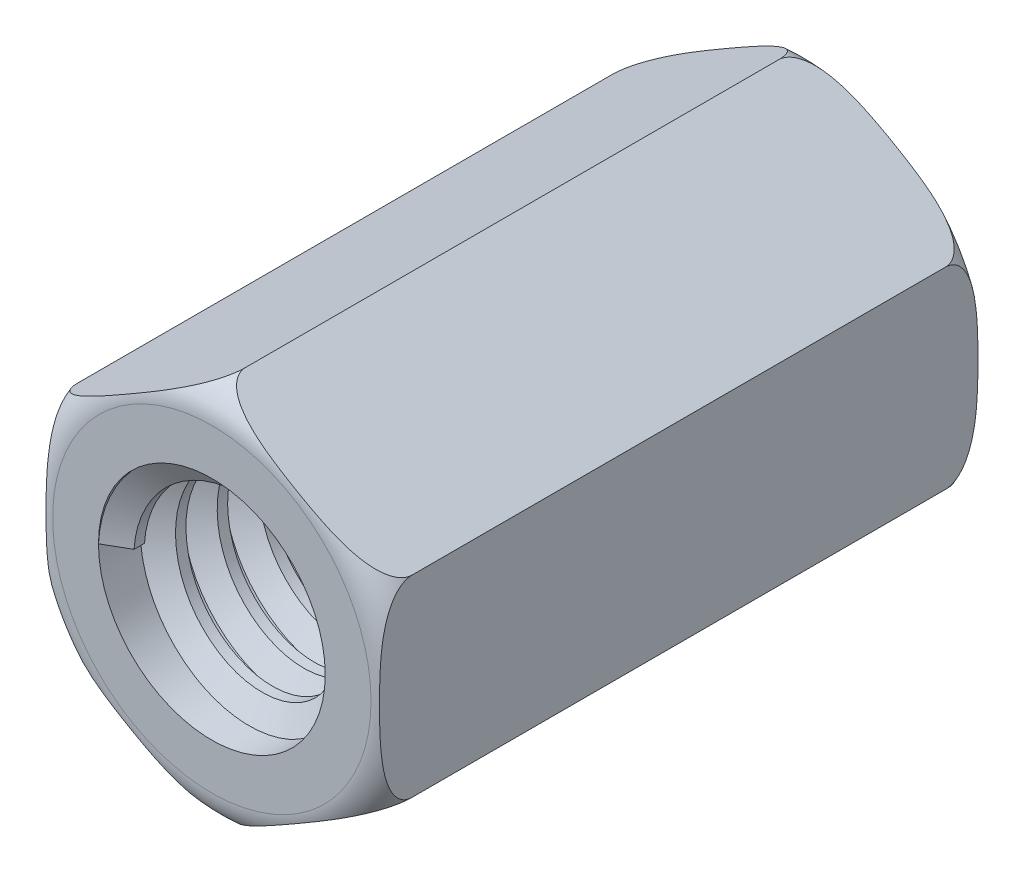
SolidWorks part; units mm, degrees
other "Coupling nut"
material "AISI 316 Annealed Stainless Steel Bar (SS)"
ref_plane "Front Plane" through (0, 0, 0) normal (0, 0, 1) x (1, 0, 0)
ref_plane "Top Plane" through (0, 0, 0) normal (0, 1, 0) x (1, 0, 0)
ref_plane "Right Plane" through (0, 0, 0) normal (1, 0, 0) x (0, 0, -1)
sketch "Sketch1" plane through (0, 0, 0) normal (0, 0, 1) x (1, 0, 0)
  line L1 (0, 5.7735) -> (-5, 2.8868)
  line L2 (-5, 2.8868) -> (-5, -2.8868)
  line L3 (-5, -2.8868) -> (0, -5.7735)
  line L4 (0, -5.7735) -> (5, -2.8868)
  line L5 (5, -2.8868) -> (5, 2.8868)
  line L6 (5, 2.8868) -> (0, 5.7735)
  circle A0 centre (0, 0) radius 5 construction
  dimension "D1" = 10
extrude "Boss Extrude" add sketch "Sketch1" along normal mid plane 18 contours L6 L1 L2 L3 L4 L5
sketch "Sketch3" plane through (0, 0, 0) normal (1, 0, 0) x (0, 0, -1)
  line L0 (-9, 0) -> (9, 0) construction
  line L1 (-9, -2.8868) -> (-9, 2.8868) construction
  line L2 (9, -2.8868) -> (9, 2.8868) construction
  line L3 (-9, 2.8868) -> (-9, 5.7735) construction
  line L4 (-9, 5.7735) -> (9, 5.7735) construction
  line L5 (-8, 5.7735) -> (-9, 5.7735)
  line L6 (-9, 5.7735) -> (-9, 4.7735)
  line L7 (0, 0) -> (0, 5.7735) construction
  line L8 (9, 5.7735) -> (9, 4.7735)
  line L9 (8, 5.7735) -> (9, 5.7735)
  arc A0 (-9, 4.7735) -> (-8, 5.7735) centre (-8, 4.7735) cw
  arc A1 (9, 4.7735) -> (8, 5.7735) centre (8, 4.7735) ccw
  dimension "D1" = 1
revolve "Cut-Revolve1" cut sketch "Sketch3" angle 360 about L0
hole_wizard "Tapped Hole" positions "Position" profile "Drill" tap size "M8" standard "ISO" end condition through all
sketch "Position" plane through (0, 0, 9) normal (0, 0, 1) x (1, 0, 0)
  point P0 (0, 0)
sketch "Drill" plane through (0, 0, 9) normal (1, 0, 0) x (0, -1, 0)
  line L0 (0, 0) -> (0, 18)
  line L1 (0, 18) -> (3.4, 18)
  line L2 (3.4, 18) -> (3.4, 0)
  line L5 (3.4, 0) -> (0, 0)
  line L11 (0, -6.35) -> (0, 107.95) construction
  dimension "Thru Tap Drill Dia." = 6.8
  dimension "Thru Tap Drill Depth" = 18
cosmetic thread "Hole Thread" parameters "D2"=8
thread "Thread1" pitch 1.25 method extrude profile "Thread Profile2" start angle 0, offset 0, length 16.75, pitch 1.25, diameter 6.8
ref_plane "Plane2" through (-3.4, 0, 9) normal (0, -1, 0) x (-1, 0, 0)
sketch "Thread Profile2" plane through (-3.4, 0, 9) normal (0, -1, 0) x (-1, 0, 0)
  line L0 (0, 0) -> (0, 1.25) construction
  line L11 (0, 0) -> (0, 1.0937)
  line L12 (0, 1.0937) -> (-0.6766, 0.7031)
  line L13 (-0.6766, 0.7031) -> (-0.6766, 0.3906)
  line L15 (-0.6766, 0.3906) -> (0, 0)
  line L17 (-0.6766, 0.5469) -> (0, 0.5469) construction
  point P2 (0, 0)
  dimension "Pitch" = 1.25
  dimension "Profile_Angle" = 60
  dimension "Profile_Land" = 0.3125
  dimension "Profile_Height" = 0.6766
